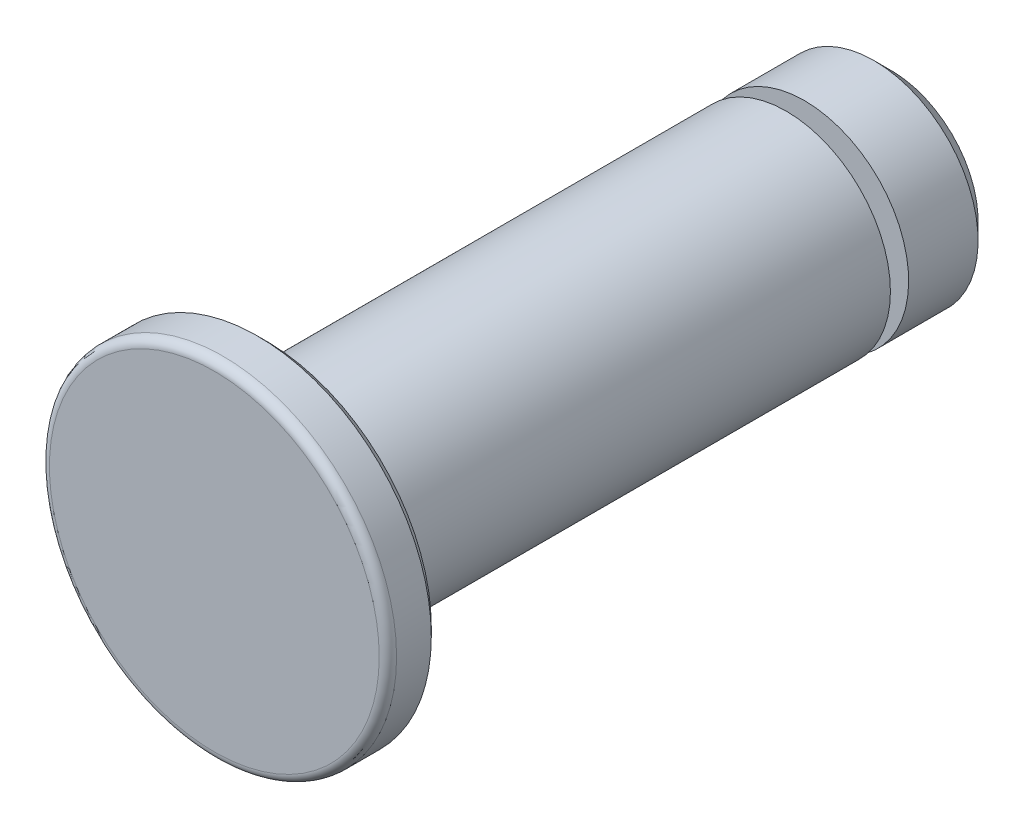
SolidWorks part; units mm, degrees
ref_plane "Front Plane" through (0, 0, 0) normal (0, 0, 1) x (1, 0, 0)
ref_plane "Top Plane" through (0, 0, 0) normal (0, 1, 0) x (1, 0, 0)
ref_plane "Right Plane" through (0, 0, 0) normal (1, 0, 0) x (0, 0, -1)
sketch "Sketch1" plane through (0, 0, 0) normal (0, 0, 1) x (1, 0, 0)
  circle A0 centre (0, 0) radius 10
  dimension "D1" = 20
extrude "Boss-Extrude1" add sketch "Sketch1" along normal blind 3
fillet "Fillet1" radius 0.5 1 edges at (10, 0, 3)
sketch "Sketch2" plane through (0, 0, 0) normal (0, 0, -1) x (-1, 0, 0)
  circle A0 centre (0, 0) radius 6
  dimension "D1" = 12
extrude "Boss-Extrude2" add sketch "Sketch2" along normal blind 31
chamfer "Chamfer1" distance 0.5 angle 45 2 edges at (10, 0, 0) (-6, 0, 0)
sketch "Sketch3" plane through (0, 0, -31) normal (0, 0, -1) x (-1, 0, 0)
  circle A0 centre (0, 0) radius 6 construction
  circle A1 centre (0, 0) radius 6
extrude "Boss-Extrude3" add sketch "Sketch3" along normal blind 5
sketch "Sketch4" plane through (0, 0, 0) normal (1, 0, 0) x (0, 0, -1)
  line L0 (36, 6) -> (0.5, 6) construction
  line L1 (36, 6) -> (0.5, 6)
  line L2 (36, -6) -> (36, 6) construction
  line L3 (36, -6) -> (36, 6)
  line L4 (36, 0) -> (17.3221, 0) construction
  line L5 (29.95, 6) -> (31, 6)
  line L6 (29.95, 6) -> (29.95, 4)
  line L7 (29.95, 4) -> (31, 4)
  line L8 (31, 6) -> (31, 4)
  dimension "D1" = 1.05
  dimension "D2" = 2
  dimension "D3" = 5
revolve "Cut-Revolve1" cut sketch "Sketch4" angle 360 about L4 region at (0, 5, -30.475)
chamfer "Chamfer2" distance 1 angle 45 1 edges at (-6, 0, -36)
